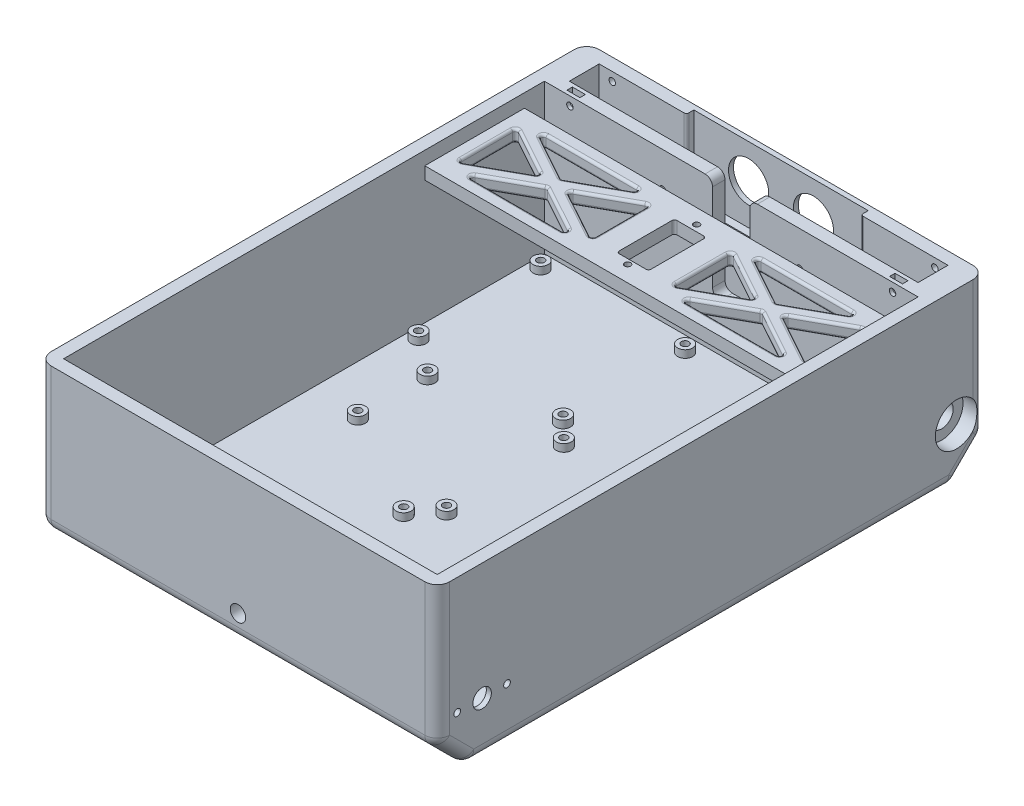
SolidWorks part; units mm, degrees
ref_plane "Front Plane" through (0, 0, 0) normal (0, 0, 1) x (1, 0, 0)
ref_plane "Top Plane" through (0, 0, 0) normal (0, 1, 0) x (1, 0, 0)
ref_plane "Right Plane" through (0, 0, 0) normal (1, 0, 0) x (0, 0, -1)
sketch "Main Body" plane through (0, 0, 0) normal (0, 1, 0) x (1, 0, 0)
  line L0 (-75, 110) -> (75, 110)
  line L1 (-75, -105) -> (75, -105)
  line L2 (-75, -105) -> (-75, 105)
  line L3 (-75, 105) -> (75, 105)
  line L4 (75, -105) -> (75, 105)
  line L5 (-75, -105) -> (75, 105) construction
  line L6 (-75, 105) -> (75, -105) construction
  line L7 (80, -105) -> (80, 105)
  line L8 (-75, -110) -> (75, -110)
  line L9 (-80, -105) -> (-80, 105)
  line L10 (-80, -110) -> (80, -110) construction
  line L11 (-80, -110) -> (-80, 110) construction
  line L12 (80, -110) -> (80, 110) construction
  line L13 (-80, 110) -> (80, 110) construction
  arc A0 (-75, -110) -> (-80, -105) centre (-75, -105) cw
  arc A1 (80, -105) -> (75, -110) centre (75, -105) cw
  arc A2 (75, 110) -> (80, 105) centre (75, 105) cw
  arc A3 (-75, 110) -> (-80, 105) centre (-75, 105) ccw
  point P0 (0, 0)
  dimension "D4" = 5
  dimension "D1" = 75
  dimension "D2" = 210
  dimension "D3" = 5
extrude "Boss-Extrude1" add sketch "Main Body" along normal blind 8 contours L1 L4 L3 L2 | L9 L8 L7 L0 L4 L1 L2 L3 region at (0, 0, -107.2797) region at (0, 0, 0)
extrude "Boss-Extrude3" add sketch "Main Body<4>" along normal blind 60 from surface starting at face at (0, 8, 0)
sketch "Main Body<4>" plane through (0, 0, 0) normal (0, 1, 0) x (1, 0, 0) same geometry as "Main Body"
sketch "Sketch1" plane through (75, 0, 0) normal (-1, 0, 0) x (0, 0, 1)
  line L0 (105, 68) -> (105, 8) construction
  line L1 (-105, 8) -> (105, 8) construction
  line L2 (79, 15.5) -> (105, 15.5)
  line L3 (79, 8) -> (105, 8)
  line L4 (79, 8) -> (79, 34)
  line L5 (79, 34) -> (105, 34)
  line L6 (105, 8) -> (105, 34)
  line L7 (79, 8) -> (105, 34) construction
  line L8 (79, 34) -> (105, 8) construction
  circle A0 centre (92, 21) radius 13
  line M2 (-105, 8) -> (105, 8)
  line M3 (105, 8) -> (105, 68)
  dimension "D1" = 26
  dimension "D2" = 7.5
extrude "Boss-Extrude4" add sketch "Sketch1" along normal up to surface (150 mm away) contours A0 L4 M2 | A0 L3 M3 region at (75, 10.5201, 82.0674) region at (75, 10.5201, 101.9326) up to face at (-75, 38, 0)
sketch "Sketch2" plane through (0, 0, 0) normal (1, 0, 0) x (0, 0, -1)
  line L0 (-105, 68) -> (-105, 15.5) construction
  line L1 (-105, 8) -> (-79, 8)
  line L2 (-105, 8) -> (-105, 15.5)
  line L3 (-105, 15.5) -> (-79, 15.5)
  line L4 (-79, 8) -> (-79, 15.5)
  line L5 (105, 8) -> (-79, 8) construction
  line L6 (-79, 8) -> (-79, 15.5) construction
  line L7 (-79, 15.5) -> (-80.2208, 15.5) construction
extrude "Cut-Extrude1" cut sketch "Sketch2" against normal mid plane 12
sketch "Sketch3" plane through (0, 8, 0) normal (0, 1, 0) x (1, 0, 0)
  line L0 (75, -105) -> (-75, -105) construction
  line L1 (-4, -79) -> (-11, -79)
  line L2 (-4, -79) -> (-4, -105)
  line L3 (-4, -105) -> (-11, -105)
  line L4 (-11, -79) -> (-11, -105)
  line L5 (0, 0) -> (0, -105) construction
  line L6 (-75, -79) -> (-6, -79) construction
  line L7 (11, -79) -> (11, -105)
  line L8 (4, -105) -> (11, -105)
  line L9 (4, -79) -> (4, -105)
  line L10 (4, -79) -> (11, -79)
  line L11 (-6, -103.7792) -> (-6, -92) construction
  dimension "D1" = 5
  dimension "D2" = 4
extrude "Boss-Extrude5" add sketch "Sketch3" along normal blind 20
sketch "Sketch4" plane through (0, 8, 0) normal (0, 1, 0) x (1, 0, 0)
  line L0 (-75, -105) -> (-75, 105) construction
  line L1 (-75, 93) -> (75, 93)
  line L2 (-75, 93) -> (-75, 88)
  line L3 (-75, 88) -> (75, 88)
  line L4 (75, 93) -> (75, 88)
  line L5 (75, 105) -> (75, -105) construction
  line L6 (-75, 105) -> (75, 105) construction
  dimension "D1" = 17
  dimension "D2" = 5
extrude "Boss-Extrude6" add sketch "Sketch4" along normal up to surface (60 mm away) up to face at (0, 68, 0)
sketch "Sketch5" plane through (80, 0, 0) normal (1, 0, 0) x (0, 0, -1)
  circle A0 centre (-92, 21) radius 3.5 construction
  circle A1 centre (-92, 21) radius 3.5
  circle A2 centre (-92, 21) radius 3.7
  dimension "D1" = 0.2
extrude "Cut-Extrude4" cut sketch "Sketch5" against normal up to next contours A1 | A2 A1 region at (80, 21, 92) region at (80, 21, 95.5953)
sketch "Sketch6" plane through (-75, 0, 0) normal (1, 0, 0) x (0, 0, -1)
  circle A0 centre (-92, 21) radius 13
  dimension "D1" = 26
extrude "Cut-Extrude5" cut sketch "Sketch6" against normal offset from surface (3 mm away) 2 up to face at (-80, 34, 0)
mirror "Mirror1" about plane through (0, 0, 0) normal (1, 0, 0) of "Cut-Extrude4"
sketch "Sketch8" plane through (75, 0, 0) normal (-1, 0, 0) x (0, 0, 1)
  circle A0 centre (92, 21) radius 13
  dimension "D1" = 26
extrude "Cut-Extrude6" cut sketch "Sketch8" against normal offset from surface (3 mm away) 2 up to face at (80, 21, 88.3)
sketch "Sketch10" plane through (80, 0, 0) normal (1, 0, 0) x (0, 0, -1)
  circle A1 centre (-82, 21) radius 1.25
  circle A2 centre (-82, 21) radius 1.25
  circle A3 centre (-102, 21) radius 1.25
  circle A4 centre (-102, 21) radius 1.25
  circle A5 centre (-92, 21) radius 12.5
  circle A6 centre (-92, 21) radius 12.5
  circle A63 centre (-102, 21) radius 1.35
  circle A64 centre (-82, 21) radius 1.35
  dimension "D1" = 0
  dimension "D2" = 0
  dimension "D3" = 0
  dimension "D4" = 0.1
  dimension "D5" = 0.1
extrude "Cut-Extrude7" cut sketch "Sketch10" against normal up to next contours A2 | A64 A2 | A4 | A63 A4 region at (80, 21, 82) region at (80, 21, 102) region at (80, 21, 103.3118) region at (80, 21, 83.3118)
mirror "Mirror3" about plane through (0, 0, 0) normal (1, 0, 0) of "Cut-Extrude7"
sketch "Sketch11" plane through (80, 0, 0) normal (1, 0, 0) x (0, 0, -1)
  circle A0 centre (98.5, 21) radius 4.5 construction
  circle A1 centre (98.5, 21) radius 4.5
  circle A3 centre (98.5, 21) radius 4.6
  dimension "D1" = 0.1
extrude "Cut-Extrude10" cut sketch "Sketch11" against normal through all contours A1 | A3 A1 region at (80, 21, -98.5) region at (80, 21, -93.913)
sketch "Sketch12" plane through (-75, 0, 0) normal (1, 0, 0) x (0, 0, -1)
  line L0 (93, 8) -> (105, 8) construction
  line L1 (93, 68) -> (105, 68)
  line L2 (93, 68) -> (93, 8)
  line L3 (93, 8) -> (105, 8)
  line L4 (105, 68) -> (105, 8)
  line L6 (93, 68) -> (93, 8) construction
  line L7 (93, 68) -> (105, 68) construction
  circle A2 centre (98.5, 21) radius 4.6 construction
  circle A3 centre (98.5, 21) radius 4.6
extrude "Boss-Extrude7" add sketch "Sketch12" along normal blind 5
sketch "Sketch13" plane through (-80, 0, 0) normal (-1, 0, 0) x (0, 0, 1)
  circle A0 centre (-98.5, 21) radius 8.55
  circle A2 centre (-98.5, 21) radius 4.6 construction
  dimension "D1" = 17.1
extrude "Cut-Extrude11" cut sketch "Sketch13" against normal blind 6
mirror "Mirror4" about plane through (0, 0, 0) normal (1, 0, 0) of "Boss-Extrude7", "Cut-Extrude11"
sketch "Sketch14" plane through (0, 8, 0) normal (0, 1, 0) x (1, 0, 0)
  line L0 (-4, -105) -> (-4, -79) construction
  line L1 (-4, -95) -> (4, -95)
  line L2 (-4, -95) -> (-4, -105)
  line L3 (-4, -105) -> (4, -105)
  line L4 (4, -95) -> (4, -105)
  dimension "D1" = 10
extrude "Boss-Extrude9" add sketch "Sketch14" along normal blind 5
sketch "Sketch15" plane through (0, 0, 110) normal (0, 0, 1) x (1, 0, 0)
  arc A0 (-3, 19.5) -> (3, 19.5) centre (0, 19.5) ccw construction
  arc A1 (-3, 19.5) -> (3, 19.5) centre (0, 19.5) ccw
  arc A2 (3, 19.5) -> (-3, 19.5) centre (0, 19.5) ccw construction
  arc A3 (3, 19.5) -> (-3, 19.5) centre (0, 19.5) ccw
  arc A4 (3.1, 19.5) -> (-3.1, 19.5) centre (0, 19.5) ccw
  arc A5 (-3.1, 19.5) -> (3.1, 19.5) centre (0, 19.5) ccw
  dimension "D1" = 0.1
extrude "Cut-Extrude12" cut sketch "Sketch15" against normal up to next contours A1 A3 | A4 A5 A3 A1 region at (0, 19.5, 110) region at (0, 16.4877, 110)
sketch "Sketch16" plane through (0, 0, 0) normal (0, -1, 0) x (1, 0, 0)
  circle A0 centre (-12.5, -82) radius 1.475 construction
  circle A1 centre (-70.5, -82) radius 1.475 construction
  circle A2 centre (-70.5, -33) radius 1.475 construction
  circle A3 centre (-12.5, -33) radius 1.475 construction
  circle A4 centre (-4.2, -25) radius 1.475 construction
  circle A5 centre (-55, -21.12) radius 1.475 construction
  circle A6 centre (-55, 6.88) radius 1.475 construction
  circle A7 centre (-4.2, 22.08) radius 1.475 construction
  circle A8 centre (-12.3, 31.18) radius 1.475 construction
  circle A9 centre (24.2, 31.18) radius 1.475 construction
  circle A10 centre (37.8459, 24.117) radius 1.475 construction
  circle A11 centre (59.5541, 24.117) radius 1.475 construction
  circle A12 centre (59.5541, 68.243) radius 1.475 construction
  circle A13 centre (37.8459, 68.243) radius 1.475 construction
  circle A14 centre (24.2, 67.68) radius 1.475 construction
  circle A15 centre (-12.3, 67.68) radius 1.475 construction
  circle A16 centre (-12.5, -82) radius 1.475
  circle A17 centre (-70.5, -82) radius 1.475
  circle A18 centre (-70.5, -33) radius 1.475
  circle A19 centre (-12.5, -33) radius 1.475
  circle A20 centre (-4.2, -25) radius 1.475
  circle A21 centre (-55, -21.12) radius 1.475
  circle A22 centre (-55, 6.88) radius 1.475
  circle A23 centre (-4.2, 22.08) radius 1.475
  circle A24 centre (-12.3, 31.18) radius 1.475
  circle A25 centre (24.2, 31.18) radius 1.475
  circle A26 centre (37.8459, 24.117) radius 1.475
  circle A27 centre (59.5541, 24.117) radius 1.475
  circle A28 centre (59.5541, 68.243) radius 1.475
  circle A29 centre (37.8459, 68.243) radius 1.475
  circle A30 centre (24.2, 67.68) radius 1.475
  circle A31 centre (-12.3, 67.68) radius 1.475
extrude "Cut-Extrude13" cut sketch "Sketch16" against normal up to next
sketch "Sketch17" plane through (0, 8, 0) normal (0, 1, 0) x (1, 0, 0)
  line L0 (0, 88) -> (0, -110) construction
  line L1 (-75, 88) -> (75, 88) construction
  line L2 (75, -110) -> (-75, -110) construction
  line L3 (-75, 4.5) -> (75, 4.5) construction
  line L7 (-75, -79) -> (-75, 88) construction
  line L8 (75, 88) -> (75, -79) construction
  circle A0 centre (-70.5, 82) radius 3
  circle A1 centre (-12.5, 82) radius 3
  circle A2 centre (-12.3, -67.68) radius 1.475
  circle A3 centre (-12.3, -67.68) radius 1.475
  circle A4 centre (24.2, -67.68) radius 1.475
  circle A5 centre (24.2, -67.68) radius 1.475
  circle A6 centre (37.8459, -68.243) radius 1.475
  circle A7 centre (37.8459, -68.243) radius 1.475
  circle A8 centre (59.5541, -68.243) radius 1.475
  circle A9 centre (59.5541, -68.243) radius 1.475
  circle A10 centre (59.5541, -24.117) radius 1.475
  circle A11 centre (59.5541, -24.117) radius 1.475
  circle A12 centre (37.8459, -24.117) radius 1.475
  circle A13 centre (37.8459, -24.117) radius 1.475
  circle A14 centre (24.2, -31.18) radius 1.475
  circle A15 centre (24.2, -31.18) radius 1.475
  circle A16 centre (-12.3, -31.18) radius 1.475
  circle A17 centre (-12.3, -31.18) radius 1.475
  circle A18 centre (-4.2, -22.08) radius 1.475
  circle A19 centre (-4.2, -22.08) radius 1.475
  circle A20 centre (-55, -6.88) radius 1.475
  circle A21 centre (-55, -6.88) radius 1.475
  circle A22 centre (-55, 21.12) radius 1.475
  circle A23 centre (-55, 21.12) radius 1.475
  circle A24 centre (-4.2, 25) radius 1.475
  circle A25 centre (-4.2, 25) radius 1.475
  circle A26 centre (-12.5, 33) radius 1.475
  circle A27 centre (-12.5, 33) radius 1.475
  circle A28 centre (-70.5, 33) radius 1.475
  circle A29 centre (-70.5, 33) radius 1.475
  circle A30 centre (-70.5, 82) radius 1.475
  circle A31 centre (-70.5, 82) radius 1.475
  circle A32 centre (-12.5, 82) radius 1.475
  circle A33 centre (-12.5, 82) radius 1.475
  circle A34 centre (-70.5, 33) radius 3
  circle A35 centre (-55, 21.12) radius 3
  circle A36 centre (-12.5, 33) radius 3
  circle A37 centre (-4.2, 25) radius 3
  circle A38 centre (-55, -6.88) radius 3
  circle A39 centre (-4.2, -22.08) radius 3
  circle A40 centre (-12.3, -31.18) radius 3
  circle A41 centre (24.2, -31.18) radius 3
  circle A42 centre (37.8459, -24.117) radius 3
  circle A43 centre (59.5541, -24.117) radius 3
  circle A44 centre (-12.3, -67.68) radius 3
  circle A45 centre (24.2, -67.68) radius 3
  circle A46 centre (37.8459, -68.243) radius 3
  circle A47 centre (59.5541, -68.243) radius 3
  dimension "D1" = 6
  dimension "D2" = 0
  dimension "D3" = 0
  dimension "D4" = 0
  dimension "D5" = 0
  dimension "D6" = 0
  dimension "D7" = 0
  dimension "D8" = 0
  dimension "D9" = 0
  dimension "D10" = 0
  dimension "D11" = 0
  dimension "D12" = 0
  dimension "D13" = 0
  dimension "D14" = 0
  dimension "D15" = 0
  dimension "D16" = 0
  dimension "D17" = 0
extrude "Boss-Extrude10" add sketch "Sketch17" along normal blind 3
sketch "Sketch18" plane through (75, 0, 0) normal (-1, 0, 0) x (0, 0, 1)
  line L1 (-80, 62.6) -> (-40, 62.6)
  line L2 (-80, 62.6) -> (-80, 57.6)
  line L3 (-80, 57.6) -> (-40, 57.6)
  line L4 (-40, 62.6) -> (-40, 57.6)
  line L5 (-88, 68) -> (105, 68) construction
  dimension "D1" = 5
  dimension "D2" = 30
  dimension "D3" = 40
  dimension "D4" = 5.4
extrude "Boss-Extrude11" add sketch "Sketch18" along normal up to next
sketch "Sketch19" plane through (0, 68, 0) normal (0, 1, 0) x (1, 0, 0)
  line L1 (-6.375, 71.575) -> (6.375, 71.575)
  line L2 (-6.375, 71.575) -> (-6.375, 48.425)
  line L3 (-6.375, 48.425) -> (6.375, 48.425)
  line L4 (6.375, 71.575) -> (6.375, 48.425)
  line L12 (-75, 80) -> (-75, 40)
  line L13 (-75, 40) -> (75, 40)
  line L14 (75, 40) -> (75, 80)
  line L15 (75, 80) -> (-75, 80)
  line L16 (-75, 80) -> (-75, 40)
  line L17 (-75, 40) -> (75, 40)
  line L18 (75, 40) -> (75, 80)
  line L19 (75, 80) -> (-75, 80)
  point P4 (0, 71.575)
  point P8 (0, 80)
  point P12 (6.375, 60)
  point P13 (75, 60)
  dimension "D1" = 23.15
  dimension "D2" = 12.75
  dimension "D3" = 0
extrude "Cut-Extrude14" cut sketch "Sketch19" against normal up to next contours L4 L1 L2 L3 region at (0, 68, -60)
sketch "Sketch21" plane through (0, 0, -110) normal (0, 0, -1) x (-1, 0, 0)
  circle A1 centre (-64.75, 64.5) radius 1.3
  circle A2 centre (-64.75, 64.5) radius 1.3
  circle A3 centre (64.75, 64.5) radius 1.3
  circle A4 centre (64.75, 64.5) radius 1.3
  dimension "D1" = 0
  dimension "D2" = 0
extrude "Cut-Extrude16" cut sketch "Sketch21" against normal up to surface (22 mm away) up to face at (0, 38, -88)
ref_plane "Plane1" through (0, 0, -90.5) normal (0, 0, -1) x (-1, 0, 0)
sketch "Sketch22" plane through (0, 0, -90.5) normal (0, 0, -1) x (-1, 0, 0)
  line L0 (-67.35, 66.0011) -> (-67.35, 68)
  line L1 (-62.15, 66.0011) -> (-64.75, 67.5022)
  line L2 (-64.75, 67.5022) -> (-67.35, 66.0011)
  line L3 (-67.35, 66.0011) -> (-67.35, 62.9989)
  line L4 (-67.35, 62.9989) -> (-64.75, 61.4978)
  line L5 (-64.75, 61.4978) -> (-62.15, 62.9989)
  line L6 (-62.15, 62.9989) -> (-62.15, 66.0011)
  line L7 (-67.35, 68) -> (-62.15, 68)
  line L8 (-62.15, 68) -> (-62.15, 66.0011)
  line L9 (70, 68) -> (-70, 68) construction
  line L10 (0, 0) -> (0, 68) construction
  line L11 (75, 68) -> (-75, 68) construction
  line L12 (64.75, 61.4978) -> (62.15, 62.9989)
  line L13 (67.35, 62.9989) -> (64.75, 61.4978)
  line L14 (64.75, 67.5022) -> (67.35, 66.0011)
  line L15 (67.35, 66.0011) -> (67.35, 62.9989)
  line L16 (67.35, 66.0011) -> (67.35, 68)
  line L17 (62.15, 62.9989) -> (62.15, 66.0011)
  line L18 (62.15, 68) -> (62.15, 66.0011)
  line L19 (67.35, 68) -> (62.15, 68)
  line L20 (62.15, 66.0011) -> (64.75, 67.5022)
  circle A0 centre (-64.75, 64.5) radius 2.6 construction
  dimension "D1" = 5.2
extrude "Cut-Extrude17" cut sketch "Sketch22" against normal mid plane 2.2 contours L20 L17 L12 L13 L15 L14 | L18 L20 L14 L16 L19 | L5 L6 L1 L2 L3 L4 | L8 L7 L0 L2 L1 region at (67.2943, 67.0006, -90.5) region at (64.75, 64.5, -90.5) region at (-64.75, 64.5, -90.5) region at (-62.2057, 67.0006, -90.5)
sketch "Sketch23" plane through (0, 0, -110) normal (0, 0, -1) x (-1, 0, 0)
  circle A0 centre (64.75, 64.5) radius 2.5
  circle A1 centre (-64.75, 64.5) radius 2.5
  dimension "D1" = 5
  dimension "D2" = 5
extrude "Cut-Extrude18" cut sketch "Sketch23" against normal mid plane 2.5
sketch "Sketch24" plane through (0, 62.6, 0) normal (0, 1, 0) x (1, 0, 0)
  circle A0 centre (0, 46.425) radius 1.2002
  arc A1 (0.4, 45.5083) -> (-0.4, 45.5083) centre (0, 46.425) ccw construction
  circle A2 centre (0, 74.125) radius 1.2002
  arc A3 (-0.4, 75.0417) -> (0, 73.1248) centre (0, 74.125) ccw construction
  point P5 (0.4, 45.5083)
  dimension "D1" = 0.2
extrude "Cut-Extrude19" cut sketch "Sketch24" against normal up to next
sketch "Sketch25" plane through (0, 62.6, 0) normal (0, 1, 0) x (1, 0, 0)
  line L1 (-11.3, 80) -> (11.3, 80)
  line L2 (-11.3, 80) -> (-11.3, 40)
  line L3 (-11.3, 40) -> (11.3, 40)
  line L4 (-75, 80) -> (-75, 40)
  line L5 (-75, 40) -> (75, 40)
  line L6 (75, 40) -> (75, 80)
  line L7 (75, 80) -> (-75, 80)
  line L8 (-75, 80) -> (-75, 40)
  line L9 (-75, 40) -> (75, 40)
  line L10 (75, 40) -> (75, 80)
  line L11 (75, 80) -> (-75, 80)
  line L12 (11.3, 80) -> (11.3, 40)
  line L13 (-11.3, 80) -> (11.3, 40) construction
  line L14 (-11.3, 40) -> (11.3, 80) construction
  line L15 (0, 80) -> (0, 40) construction
  line L16 (70, 75) -> (70, 45)
  line L17 (-70, 75) -> (-16.3, 75)
  line L18 (-70, 75) -> (-70, 45)
  line L19 (-70, 45) -> (-16.3, 45)
  line L20 (-16.3, 75) -> (-16.3, 45)
  line L21 (-70, 75) -> (-16.3, 45) construction
  line L22 (-70, 45) -> (-16.3, 75) construction
  line L23 (70, 75) -> (16.3, 45) construction
  line L24 (70, 45) -> (16.3, 75) construction
  line L25 (70, 75) -> (16.3, 75)
  line L26 (16.3, 75) -> (16.3, 45)
  line L27 (70, 45) -> (16.3, 45)
  line L28 (-75, 60) -> (-11.3, 60) construction
  line L29 (75, 60) -> (11.3, 60) construction
  line L30 (-70, 71.9362) -> (-48.3314, 60)
  line L31 (-16.3, 71.9362) -> (-37.9686, 60)
  line L32 (70, 71.9362) -> (48.3314, 60)
  line L33 (-48.3314, 60) -> (-70, 48.0638)
  line L34 (48.3314, 60) -> (70, 48.0638)
  line L35 (-65.199, 45) -> (-43.15, 57.1458)
  line L36 (65.199, 45) -> (43.15, 57.1458)
  line L37 (-43.15, 57.1458) -> (-21.101, 45)
  line L38 (43.15, 57.1458) -> (21.101, 45)
  line L39 (16.3, 71.9362) -> (37.9686, 60)
  line L40 (-37.9686, 60) -> (-16.3, 48.0638)
  line L41 (37.9686, 60) -> (16.3, 48.0638)
  line L42 (-65.199, 75) -> (-43.15, 62.8542)
  line L43 (65.199, 75) -> (43.15, 62.8542)
  line L44 (-43.15, 62.8542) -> (-21.101, 75)
  line L45 (43.15, 62.8542) -> (21.101, 75)
  line L46 (-75, 40) -> (-75, 80) construction
  line L47 (-75, 40) -> (75, 40) construction
  point P2 (0, 60)
  point P9 (-43.15, 60)
  point P10 (75, 60)
  point P24 (43.15, 60)
  point P62 (-54.1745, 68.9271)
  dimension "D2" = 150
  dimension "D3" = 5
  dimension "D4" = 5
  dimension "D5" = 5
  dimension "D6" = 26.6686
  dimension "D7" = 96.101
  dimension "D1" = 0
extrude "Cut-Extrude21" cut sketch "Sketch25" against normal up to next contours L37 L35 L19 | L33 L30 L18 | L42 L44 L17 | L31 L40 L20 | L41 L39 L26 | L45 L43 L25 | L36 L38 L27 | L32 L34 L16 region at (62.7771, 62.6, -60) region at (43.15, 62.6, -70.9514) region at (43.15, 62.6, -49.0486) region at (23.5229, 62.6, -60) region at (-43.15, 62.6, -70.9514) region at (-62.7771, 62.6, -60) region at (-23.5229, 62.6, -60) region at (-43.15, 62.6, -49.0486)
sketch "Sketch26" plane through (-80, 0, 0) normal (-1, 0, 0) x (0, 0, 1)
  line L0 (-110, 12.58) -> (-97.42, 0)
  line L1 (-110, 68) -> (-110, 0) construction
  line L2 (105, 0) -> (-105, 0) construction
  line L3 (-97.42, 0) -> (-92.42, 0)
  line L4 (-92.42, 0) -> (-110, 17.58)
  line L5 (-110, 17.58) -> (-110, 12.58)
  line L6 (-110, 12.58) -> (-110, 0)
  line L7 (-110, 0) -> (-97.42, 0)
  circle A1 centre (-98.5, 21) radius 8.55 construction
  line M5 (-105, 15.4455) -> (-105, 0)
  line M6 (-105, 0) -> (105, 0)
  dimension "D1" = 2
  dimension "D2" = 5
  dimension "D3" = 45
extrude "Cut-Extrude22" cut sketch "Sketch26" against normal up to next contours L6 L7 L0 M5 | L0 M5 M6 region at (-80, 5.1434, -107.7067) region at (-80, 2.5267, -102.4733)
mirror "Mirror5" about plane through (0, 0, 0) normal (0, 0, 1) of "Cut-Extrude22"
fillet "Fillet1" radius 5 14 edges at (80, 3.79, -101.21) (78.5355, 11.1156, -108.5355) (-80, 3.79, -101.21) (-78.5355, 11.1156, -108.5355) (80, 3.79, 101.21) (78.5355, 11.1156, 108.5355) (-80, 3.79, 101.21) (-78.5355, 11.1156, 108.5355) (0, 0, -97.42) (0, 12.58, -110) (0, 0, 97.42) (0, 12.58, 110) (-80, 0, 0) (80, 0, 0)
fillet "Fillet2" radius 1 76 edges at (-32.1255, 57.6, -51.0729) (-32.1255, 62.6, -51.0729) (-21.101, 60.1, -45) (-43.15, 62.6, -45) (-43.15, 57.6, -45) (-54.1745, 57.6, -51.0729) (-65.199, 60.1, -45) (-54.1745, 62.6, -51.0729) (-43.15, 60.1, -57.1458) (32.1255, 57.6, -68.9271) (32.1255, 62.6, -68.9271) (21.101, 60.1, -75) (43.15, 62.6, -75) (43.15, 57.6, -75) (54.1745, 57.6, -68.9271) (65.199, 60.1, -75) (54.1745, 62.6, -68.9271) (43.15, 60.1, -62.8542) (54.1745, 62.6, -51.0729) (54.1745, 57.6, -51.0729) (43.15, 57.6, -45) (65.199, 60.1, -45) (43.15, 62.6, -45) (21.101, 60.1, -45) (32.1255, 62.6, -51.0729) (43.15, 60.1, -57.1458) (32.1255, 57.6, -51.0729) (59.1657, 62.6, -65.9681) (59.1657, 57.6, -65.9681) (70, 57.6, -60) (70, 60.1, -71.9362) (70, 62.6, -60) (70, 60.1, -48.0638) (59.1657, 62.6, -54.0319) (48.3314, 60.1, -60) (59.1657, 57.6, -54.0319) (-54.1745, 62.6, -68.9271) (-54.1745, 57.6, -68.9271) (-43.15, 57.6, -75) (-65.199, 60.1, -75) (-43.15, 62.6, -75) (-21.101, 60.1, -75) (-32.1255, 62.6, -68.9271) (-43.15, 60.1, -62.8542) (-32.1255, 57.6, -68.9271) (-59.1657, 57.6, -54.0319) (-59.1657, 62.6, -54.0319) (-70, 60.1, -48.0638) (-70, 62.6, -60) (-70, 57.6, -60) (-59.1657, 57.6, -65.9681) (-70, 60.1, -71.9362) (-59.1657, 62.6, -65.9681) (-48.3314, 60.1, -60) (-27.1343, 62.6, -65.9681) (-27.1343, 57.6, -65.9681) (-16.3, 57.6, -60) (-16.3, 60.1, -71.9362) (-16.3, 62.6, -60) (-16.3, 60.1, -48.0638) (-27.1343, 62.6, -54.0319) (-37.9686, 60.1, -60) (-27.1343, 57.6, -54.0319) (27.1343, 57.6, -54.0319) (27.1343, 62.6, -54.0319) (16.3, 60.1, -48.0638) (16.3, 62.6, -60) (16.3, 57.6, -60) (27.1343, 57.6, -65.9681) (16.3, 60.1, -71.9362) (27.1343, 62.6, -65.9681) (37.9686, 60.1, -60) (6.375, 60.1, -48.425) (-6.375, 60.1, -48.425) (-6.375, 60.1, -71.575) (6.375, 60.1, -71.575)
sketch "Sketch33" plane through (0, 0, -110) normal (0, 0, -1) x (-1, 0, 0)
  circle A0 centre (-13, 53.9999) radius 8.075
  circle A1 centre (13, 53.9999) radius 8.075
  circle A2 centre (-13, 53.9999) radius 7.3 construction
  circle A3 centre (13, 53.9999) radius 7.3 construction
  dimension "D1" = 16.15
extrude "Cut-Extrude27" cut sketch "Sketch33" against normal up to next
sketch "Sketch34" plane through (0, 0, -93) normal (0, 0, -1) x (-1, 0, 0)
  circle A0 centre (27.525, 54) radius 1.3 construction
  circle A1 centre (27.525, 54) radius 1.3
  circle A2 centre (-27.525, 54) radius 1.3 construction
  circle A3 centre (-27.525, 54) radius 1.3
extrude "Cut-Extrude28" cut sketch "Sketch34" against normal up to next
sketch "Sketch35" plane through (0, 68, 0) normal (0, 1, 0) x (1, 0, 0)
  line L0 (70, 93) -> (-70, 93) construction
  line L1 (-7.5, 93) -> (7.5, 93)
  line L2 (-7.5, 93) -> (-7.5, 88)
  line L3 (-7.5, 88) -> (7.5, 88)
  line L4 (7.5, 93) -> (7.5, 88)
  line L5 (-7.5, 93) -> (7.5, 88) construction
  line L6 (-7.5, 88) -> (7.5, 93) construction
  line L7 (-75, 88) -> (75, 88) construction
  point P0 (0, 90.5)
  dimension "D1" = 15
extrude "Cut-Extrude29" cut sketch "Sketch35" against normal offset from surface (41 mm away) 19 up to face at (37.8459, 8, 71.243)
fillet "Fillet4" radius 3 9 edges at (0, 8, 95) (-7.5, 28, 79) (-7.5, 28, 105) (7.5, 28, 105) (7.5, 28, 79) (-7.5, 68, -90.5) (7.5, 68, -90.5) (-7.5, 27, -90.5) (7.5, 27, -90.5)
fillet "Fillet5" radius 1 1 edges at (0, 13, 95)
sketch "Sketch36" plane through (0, 68, 0) normal (0, 1, 0) x (1, 0, 0)
  line L0 (-70, 105) -> (70, 105) construction
  line L1 (-35, 108) -> (35, 108)
  line L2 (-35, 108) -> (-35, 105)
  line L3 (-35, 105) -> (35, 105)
  line L4 (35, 108) -> (35, 105)
  line L5 (-75, 110) -> (75, 110) construction
  point P6 (0, 108)
  dimension "D1" = 70
  dimension "D2" = 2
extrude "Cut-Extrude30" cut sketch "Sketch36" against normal blind 30
fillet "Fillet6" radius 1 2 edges at (35, 53, -105) (-35, 53, -105)
